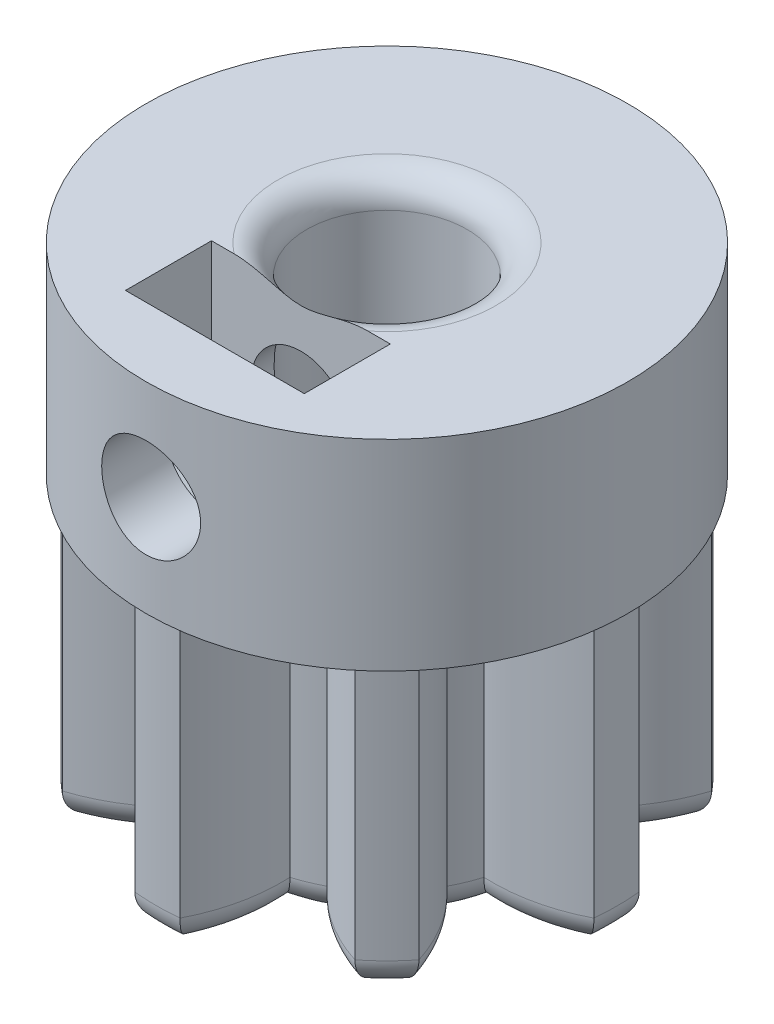
SolidWorks part; units mm, degrees
ref_plane "Alzado" through (0, 0, 0) normal (0, 0, 1) x (1, 0, 0)
ref_plane "Planta" through (0, 0, 0) normal (0, 1, 0) x (1, 0, 0)
ref_plane "Vista lateral" through (0, 0, 0) normal (1, 0, 0) x (0, 0, -1)
sketch "Croquis1" plane through (0, 0, 0) normal (0, 1, 0) x (1, 0, 0)
  arc A0 (4.4758, 2.3923) -> (6.2175, 5.1026) centre (0.3122, 6.9829) ccw
  arc A1 (6.2175, 5.1026) -> (5.1026, 6.2175) centre (0, 0) ccw
  arc A2 (5.1026, 6.2175) -> (2.3923, 4.4758) centre (6.9829, 0.3122) ccw
  arc A3 (2.3923, 4.4758) -> (1.4732, 4.8565) centre (0, 0) ccw
  arc A4 (4.8565, -1.4732) -> (8.0045, -0.7884) centre (5.1584, 4.7169) ccw
  arc A5 (8.0045, -0.7884) -> (8.0045, 0.7884) centre (0, 0) ccw
  arc A6 (1.4732, 4.8565) -> (0.7884, 8.0045) centre (-4.7169, 5.1584) ccw
  arc A7 (0.7884, 8.0045) -> (-0.7884, 8.0045) centre (0, 0) ccw
  arc A8 (-0.7884, 8.0045) -> (-1.4732, 4.8565) centre (4.7169, 5.1584) ccw
  arc A9 (-1.4732, 4.8565) -> (-2.3923, 4.4758) centre (0, 0) ccw
  arc A10 (8.0045, 0.7884) -> (4.8565, 1.4732) centre (5.1584, -4.7169) ccw
  arc A11 (4.8565, 1.4732) -> (4.4758, 2.3923) centre (0, 0) ccw
  arc A12 (2.3923, -4.4758) -> (5.1026, -6.2175) centre (6.9829, -0.3122) ccw
  arc A13 (5.1026, -6.2175) -> (6.2175, -5.1026) centre (0, 0) ccw
  arc A14 (6.2175, -5.1026) -> (4.4758, -2.3923) centre (0.3122, -6.9829) ccw
  arc A15 (4.4758, -2.3923) -> (4.8565, -1.4732) centre (0, 0) ccw
  arc A16 (-1.4732, -4.8565) -> (-0.7884, -8.0045) centre (4.7169, -5.1584) ccw
  arc A17 (-0.7884, -8.0045) -> (0.7884, -8.0045) centre (0, 0) ccw
  arc A18 (0.7884, -8.0045) -> (1.4732, -4.8565) centre (-4.7169, -5.1584) ccw
  arc A19 (1.4732, -4.8565) -> (2.3923, -4.4758) centre (0, 0) ccw
  arc A20 (-4.4758, -2.3923) -> (-6.2175, -5.1026) centre (-0.3122, -6.9829) ccw
  arc A21 (-6.2175, -5.1026) -> (-5.1026, -6.2175) centre (0, 0) ccw
  arc A22 (-5.1026, -6.2175) -> (-2.3923, -4.4758) centre (-6.9829, -0.3122) ccw
  arc A23 (-2.3923, -4.4758) -> (-1.4732, -4.8565) centre (0, 0) ccw
  arc A24 (-4.8565, 1.4732) -> (-8.0045, 0.7884) centre (-5.1584, -4.7169) ccw
  arc A25 (-8.0045, 0.7884) -> (-8.0045, -0.7884) centre (0, 0) ccw
  arc A26 (-8.0045, -0.7884) -> (-4.8565, -1.4732) centre (-5.1584, 4.7169) ccw
  arc A27 (-4.8565, -1.4732) -> (-4.4758, -2.3923) centre (0, 0) ccw
  arc A28 (-2.3923, 4.4758) -> (-5.1026, 6.2175) centre (-6.9829, 0.3122) ccw
  arc A29 (-5.1026, 6.2175) -> (-6.2175, 5.1026) centre (0, 0) ccw
  arc A30 (-6.2175, 5.1026) -> (-4.4758, 2.3923) centre (-0.3122, 6.9829) ccw
  arc A31 (-4.4758, 2.3923) -> (-4.8565, 1.4732) centre (0, 0) ccw
  circle A32 centre (0, 0) radius 8.4
  circle A33 centre (0, 0) radius 2.8
  point P62 (0, 0)
  dimension "D1" = 5.6
  dimension "D2" = 2.9464
  dimension "D4" = 6.1974
  dimension "D5" = 8.0433
  dimension "D7" = 5.075
  dimension "D9" = 16.8
  dimension "D8" = 1.5768
  dimension "D10" = 8
extrude "Saliente-Extruir1" add sketch "Croquis1" along normal blind 17 contours A32
extrude "Cortar-Extruir5" cut sketch "Croquis1<3>" along normal up to surface (17 mm away) contours A33 region at (0, 0, 0) up to face at (0, 17, 8.4)
sketch "Croquis1<3>" plane through (0, 0, 0) normal (0, 1, 0) x (1, 0, 0) same geometry as "Croquis1"
extrude "Cortar-Extruir6" cut sketch "Croquis1<4>" along normal blind 10 contours A32 A31 A30 A29 A28 A9 A8 A7 A6 A3 A2 A1 A0 A11 A10 A5 A4 A15 A14 A13 A12 A19 A18 A17 A16 A23 A22 A21 A20 A27 A26 A25 A24 region at (-8.1624, 0, 0)
sketch "Croquis1<4>" plane through (0, 0, 0) normal (0, 1, 0) x (1, 0, 0) same geometry as "Croquis1"
sketch "Croquis2" plane through (0, 0, 0) normal (0, 0, 1) x (1, 0, 0)
  line L0 (8.4, 17) -> (-8.4, 17) construction
  circle A0 centre (0, 13.5) radius 1.725
  dimension "D1" = 3.5
  dimension "D2" = 3.45
extrude "Cortar-Extruir7" cut sketch "Croquis2" along normal blind 10
ref_plane "Plano1" through (0, 0, 8) normal (0, 0, 1) x (1, 0, 0)
ref_plane "Plano2" through (0, 0, 4) normal (0, 0, 1) x (1, 0, 0)
ref_plane "Plano3" through (0, 0, 3) normal (0, 0, 1) x (1, 0, 0)
sketch "Croquis3" plane through (0, 0, 3) normal (0, 0, 1) x (1, 0, 0)
  line L0 (3.1177, 17) -> (-3.1177, 17)
  line L7 (8.4, 17) -> (-8.4, 17) construction
  line L8 (-3.1177, 11.7) -> (0, 9.9)
  line L9 (0, 9.9) -> (3.1177, 11.7)
  line L10 (3.1177, 11.7) -> (3.1177, 17)
  line L11 (3.1177, 15.3) -> (0, 17.1) construction
  line L12 (0, 17.1) -> (-3.1177, 15.3) construction
  line L13 (-3.1177, 17) -> (-3.1177, 11.7)
  line L14 (8.4, 17) -> (-8.4, 17)
  circle A0 centre (0, 13.5) radius 3.1177 construction
  dimension "D1" = 3.6
  dimension "D2" = 6.2354
extrude "Cortar-Extruir8" cut sketch "Croquis3" along normal blind 3 contours L0 L13 L8 L9 L10 region at (0, 13.8782, 3)
fillet "Redondeo1" radius 1 33 edges at (0, 0, 2.8) (-8.0433, 0, 0) (-6.4758, 0, 1.3389) (-4.6887, 0, 1.9421) (-5.5258, 0, 3.6323) (-5.6874, 0, 5.6874) (-3.6323, 0, 5.5258) (-1.9421, 0, 4.6887) (-1.3389, 0, 6.4758) (0, 0, 8.0433) (1.3389, 0, 6.4758) (1.9421, 0, 4.6887) (3.6323, 0, 5.5258) (5.6874, 0, 5.6874) (5.5258, 0, 3.6323) (4.6887, 0, 1.9421) (6.4758, 0, 1.3389) (8.0433, 0, 0) (6.4758, 0, -1.3389) (4.6887, 0, -1.9421) (5.5258, 0, -3.6323) (5.6874, 0, -5.6874) (3.6323, 0, -5.5258) (1.9421, 0, -4.6887) (1.3389, 0, -6.4758) (0, 0, -8.0433) (-1.3389, 0, -6.4758) (-1.9421, 0, -4.6887) (-3.6323, 0, -5.5258) (-5.6874, 0, -5.6874) (-5.5258, 0, -3.6323) (-4.6887, 0, -1.9421) (-6.4758, 0, -1.3389)
fillet "Redondeo2" radius 1 1 edges at (0, 17, 2.8)
